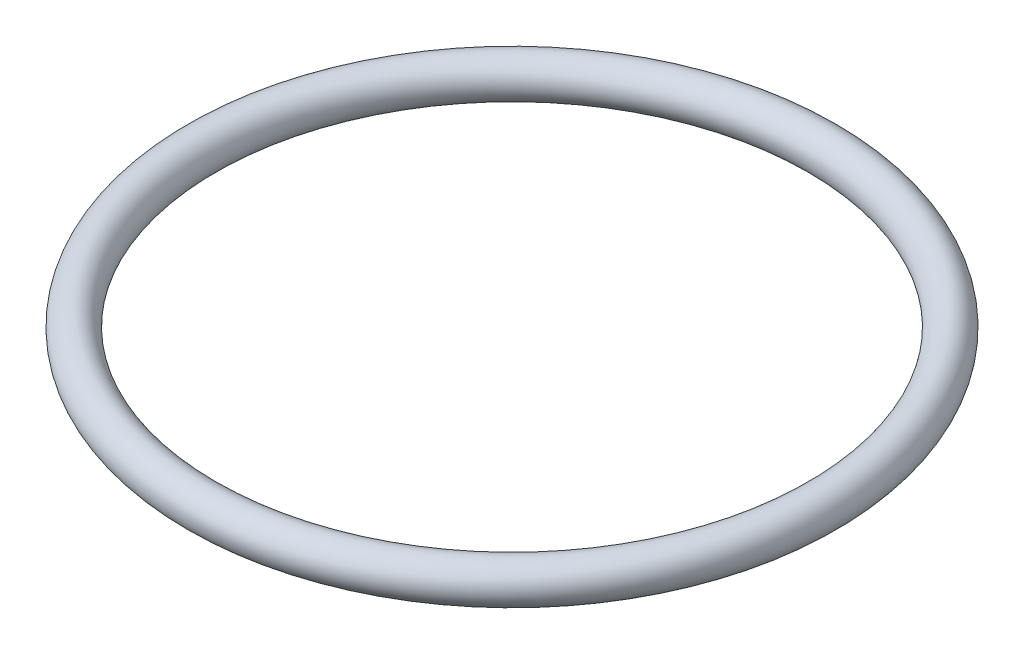
SolidWorks part; units mm, degrees
ref_plane "Alzado" through (0, 0, 0) normal (0, 0, 1) x (1, 0, 0)
ref_plane "Planta" through (0, 0, 0) normal (0, 1, 0) x (1, 0, 0)
ref_plane "Vista lateral" through (0, 0, 0) normal (1, 0, 0) x (0, 0, -1)
sketch "Croquis2" plane through (0, 0, 0) normal (1, 0, 0) x (0, 0, -1)
  line L0 (-42.035, 27.2985) -> (-42.035, -21.426) construction
  circle A0 centre (0, 0) radius 2.665
  dimension "D1" = 5.33
  dimension "D2" = 42.035
revolve "Revolución1" add sketch "Croquis2" angle 360 about L0
sketch "Croquis3" plane through (0, 0, 0) normal (1, 0, 0) x (0, 0, -1)
  line L0 (-42.035, 28.3519) -> (-42.035, -22.8114) construction
  dimension "D1" = 42.035
ref_plane "Plane1" through (0, 0, 42.04) normal (0, 0, 1) x (1, 0, 0)
ref_axis "Axis1" through (0, 38.5221, 42.04) along (0, -1, 0)
ref_plane "Plane2" through (0, 2.675, 0) normal (0, 1, 0) x (1, 0, 0)
